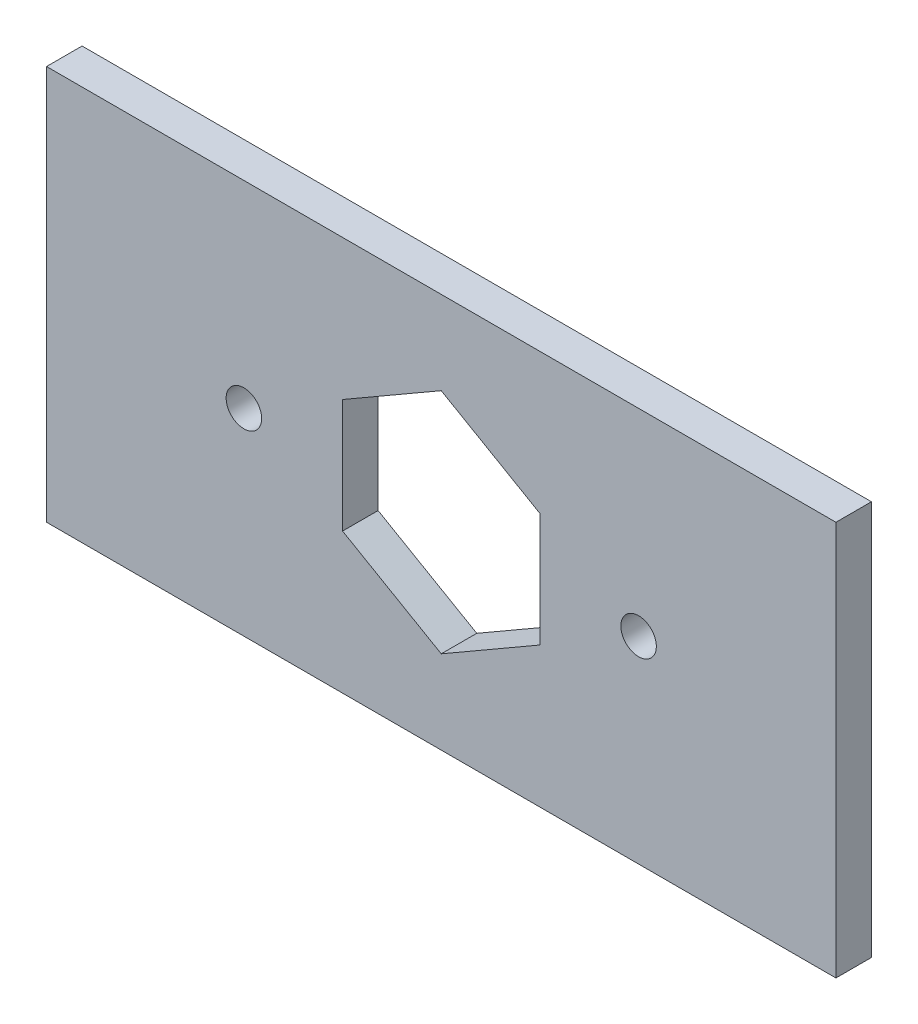
SolidWorks part; units mm, degrees
ref_plane "Front Plane" through (0, 0, 0) normal (0, 0, 1) x (1, 0, 0)
ref_plane "Top Plane" through (0, 0, 0) normal (0, 1, 0) x (1, 0, 0)
ref_plane "Right Plane" through (0, 0, 0) normal (1, 0, 0) x (0, 0, -1)
sketch "Sketch1" plane through (0, 0, 0) normal (0, 0, 1) x (1, 0, 0)
  line L1 (6.35, 3.6662) -> (0, 7.3323)
  line L2 (0, 7.3323) -> (-6.35, 3.6662)
  line L3 (-6.35, 3.6662) -> (-6.35, -3.6662)
  line L4 (-6.35, -3.6662) -> (0, -7.3323)
  line L5 (0, -7.3323) -> (6.35, -3.6662)
  line L6 (6.35, -3.6662) -> (6.35, 3.6662)
  line L7 (25.4, 12.7) -> (-25.4, 12.7)
  line L8 (25.4, 12.7) -> (25.4, -12.7)
  line L9 (25.4, -12.7) -> (-25.4, -12.7)
  line L10 (-25.4, 12.7) -> (-25.4, -12.7)
  circle A0 centre (0, 0) radius 6.35 construction
  circle A1 centre (-12.7, 0) radius 1.143
  circle A2 centre (12.7, 0) radius 1.143
  circle A3 centre (0, 0) radius 7.9375 construction
  dimension "D9" = 2.286
  dimension "D10" = 2.286
  dimension "D11" = 15.875
  dimension "D1" = 12.7
  dimension "D2" = 25.4
  dimension "D3" = 50.8
  dimension "D4" = 25.4
  dimension "D5" = 12.7
  dimension "D6" = 12.7
  dimension "D7" = 12.7
  dimension "D8" = 25.4
extrude "Boss-Extrude1" add sketch "Sketch1" along normal mid plane 2.286
